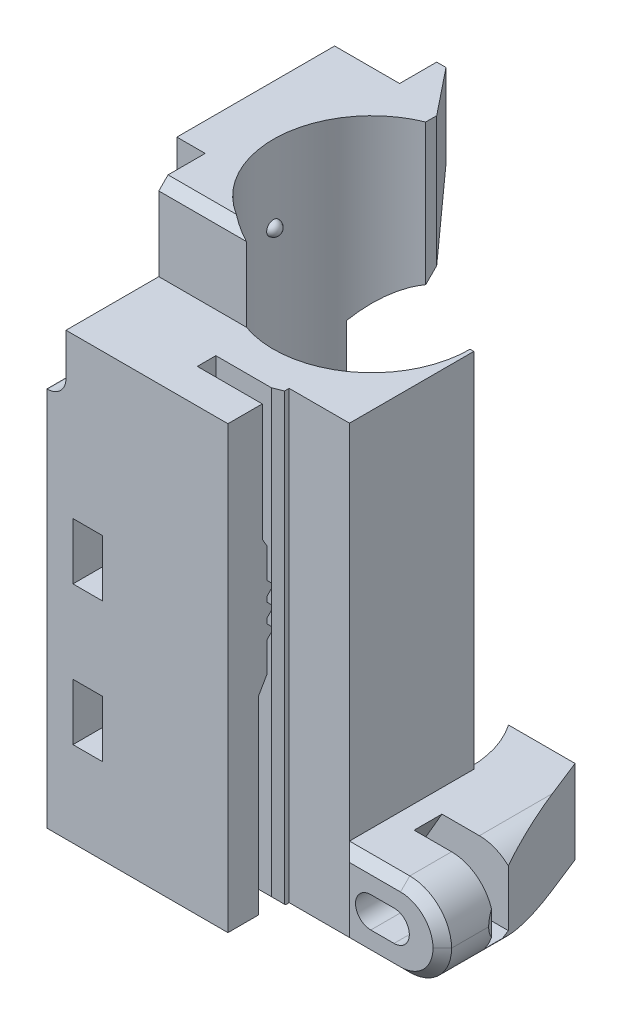
SolidWorks part; units mm, degrees
material "Custom Plastic"
ref_plane "Front Plane" through (0, 0, 0) normal (0, 0, 1) x (1, 0, 0)
ref_plane "Top Plane" through (0, 0, 0) normal (0, 1, 0) x (1, 0, 0)
ref_plane "Right Plane" through (0, 0, 0) normal (1, 0, 0) x (0, 0, -1)
sketch "Sketch2" plane through (0, 0, 0) normal (0, 1, 0) x (1, 0, 0)
  line L0 (22, -14.4) -> (22, -9.4)
  line L1 (16, 6) -> (16, -12.9) construction
  line L2 (11, -13.4) -> (4.5, -13.4)
  line L3 (4.5, -13.4) -> (4.5, -20)
  line L4 (4.5, -20) -> (-15, -20)
  line L5 (-15, -20) -> (-15, 16)
  line L6 (22, -9.4) -> (14.1647, -9.4) construction
  line L7 (8.7384, 6) -> (15.906, 6)
  line L8 (-15, 16) -> (-4, 16)
  line L9 (-4, 16) -> (-4, 9.8163)
  line L10 (11, -13.4) -> (12, -14.4)
  line L11 (12, -14.4) -> (22, -14.4)
  line L12 (22, -9.4) -> (15.906, 6)
  circle A0 centre (0, 0) radius 10.5 construction
  arc A1 (-4, 9.8163) -> (8.7384, 6) centre (0, 0) ccw
  arc A3 (14.1647, -9.4) -> (15.906, 6) centre (0, 0) ccw construction
  dimension "D1" = 21
  dimension "D2" = 0.1
  dimension "D11" = 17
  dimension "D3" = 4.5
  dimension "D4" = 16
  dimension "D5" = 15
  dimension "D6" = 13.4
  dimension "D7" = 20
  dimension "D8" = 16
  dimension "D9" = 4
  dimension "D10" = 6
  dimension "D12" = 22
  dimension "D14" = 45
  dimension "D15" = 11
  dimension "D16" = 1
extrude "Boss-Extrude1" add sketch "Sketch2" along normal blind 37 and the other way blind 20
sketch "Sketch3" plane through (0, 0, 0) normal (0, -1, 0) x (1, 0, 0)
  circle A0 centre (0, 0) radius 10.5
  dimension "D1" = 21
extrude "Cut-Extrude1" [suppressed] cut sketch "Sketch3" against normal blind 20 from offset 4 offset against normal yes
mirror "Mirror1" [suppressed] about plane through (0, 0, 0) normal (0, 1, 0)
sketch "Sketch4" plane through (0, 37, 0) normal (0, -1, 0) x (1, 0, 0)
  line L0 (4.5, 20) -> (4.5, 13.4) construction
  line L1 (-15, 20) -> (4.5, 20)
  line L2 (-15, 20) -> (-15, 9.9962)
  line L3 (-15, 9.9962) -> (4.5, 9.9962)
  line L4 (4.5, 20) -> (4.5, 9.9962)
extrude "Cut-Extrude3" [suppressed] cut sketch "Sketch4" along normal blind 11
sketch "Sketch5" plane through (4.5, 0, 0) normal (1, 0, 0) x (0, 0, -1)
  line L0 (-15.8, 5.718) -> (-15.3, 6.218)
  line L1 (-14.3, -20) -> (-16.3, -20)
  line L2 (-14.3, -20) -> (-14.3, 37)
  line L3 (-16.3, 37) -> (-14.3, 37)
  line L4 (-15.8, 2.5) -> (-15.8, 5.718)
  line L5 (-15.3, 6.218) -> (-15.3, 6.718)
  line L6 (-15.3, 6.718) -> (-15.8, 7.218)
  line L7 (-15.8, 9.782) -> (-15.3, 10.282)
  line L8 (-15.3, 10.282) -> (-15.3, 10.782)
  line L9 (-15.3, 10.782) -> (-15.8, 11.282)
  line L10 (-15.8, 7.75) -> (-15.3, 8.25)
  line L11 (-15.3, 8.25) -> (-15.3, 8.75)
  line L12 (-15.3, 8.75) -> (-15.8, 9.25)
  line L13 (-15.8, 9.25) -> (-15.8, 9.782)
  line L14 (-15.8, 2.5) -> (-16.3, 1.634)
  line L15 (-15.8, 7.218) -> (-15.8, 7.75)
  line L16 (-16.3, 1.634) -> (-16.3, -20)
  line L17 (-15.8, 11.282) -> (-15.8, 14.5)
  line L18 (-15.8, 14.5) -> (-16.3, 15.366)
  line L19 (-20, -20) -> (-13.4, -20) construction
  line L20 (16, 8.5) -> (-15.3, 8.5) construction
  line L21 (-16.3, 15.366) -> (-16.3, 37)
  line L22 (-20, 37) -> (-13.4, 37) construction
  line L23 (16, -20) -> (16, 37) construction
  dimension "D1" = 0.5
  dimension "D2" = 0.5
  dimension "D3" = 2.032
  dimension "D4" = 1.5
  dimension "D5" = 2
  dimension "D6" = 14.3
  dimension "D7" = 6
  dimension "D8" = 150
extrude "Cut-Extrude5" cut sketch "Sketch5" against normal blind 7
chamfer "Chamfer1" [suppressed] distance 1.2 angle 45
chamfer "Chamfer3" distance 0.5 angle 45 9 edges at (1, -20, 14.3) (-3.0421, -20, 10.1541) (-4, -20, -12.9082) (-9.5, -20, -16) (-15, -20, 2) (-5.25, -20, 20) (4.5, -20, 18.15) (1, -20, 16.3) (-2.5, -20, 15.3)
sketch "Sketch6" plane through (-15, 0, 0) normal (-1, 0, 0) x (0, 0, 1)
  line L0 (13, 7.5) -> (13, -7.5) construction
  line L1 (0, 0) -> (13, 0) construction
  circle A0 centre (13, 7.5) radius 1.55
  circle A1 centre (13, -7.5) radius 1.55
  dimension "D2" = 3.1
  dimension "D1" = 15
  dimension "D3" = 13
extrude "Cut-Extrude6" cut sketch "Sketch6" against normal blind 10
sketch "Sketch7" plane through (-15, 0, 0) normal (-1, 0, 0) x (0, 0, 1)
  line L0 (21.3141, -4.2) -> (21.3141, -10.3)
  line L1 (9.3668, -7.5) -> (10.9834, -10.3)
  line L2 (10.9834, -10.3) -> (21.3141, -10.3)
  line L3 (11.3834, 4.7) -> (9.7668, 7.5)
  line L4 (21.3141, 4.7) -> (11.3834, 4.7)
  line L5 (21.3141, -4.7) -> (11.3834, -4.7) construction
  line L6 (11.2721, -4.2) -> (9.3668, -7.5)
  line L7 (-3, 8.5) -> (19.4531, 8.5) construction
  line L8 (11.2721, -4.2) -> (21.3141, -4.2)
  line L9 (11.3834, 10.3) -> (21.7141, 10.3) construction
  line L10 (13.1374, -12.1691) -> (15.0359, -8.8809) construction
  line L11 (16.6078, -8.8418) -> (15.5516, -7.0123) construction
  line L12 (9.7668, 7.5) -> (11.6721, 10.8)
  line L13 (21.3141, 4.7) -> (21.3141, 10.8)
  line L14 (11.6721, 10.8) -> (21.3141, 10.8)
  circle A0 centre (12.6, -7.5) radius 2.8 construction
  circle A2 centre (13, 7.5) radius 2.8 construction
  circle A3 centre (13, 7.5) radius 1.55 construction
  point P4 (13, -7.5)
  dimension "D1" = 5.6
  dimension "D2" = 0.4
  dimension "D3" = 0.5
  dimension "D4" = 0.5
extrude "Cut-Extrude7" cut sketch "Sketch7" against normal blind 3.2 from offset 2.8 offset against normal yes
sketch "Sketch9" plane through (-15, 0, 0) normal (-1, 0, 0) x (0, 0, 1)
  line L0 (-16, 28) -> (-6, 18)
  line L1 (-16, -19.5) -> (-16, 37) construction
  line L2 (-6, 18) -> (-6, -20)
  line L3 (-16, -20) -> (20, -20) construction
  line L4 (-6, -20) -> (-16, -20)
  line L5 (-16, -20) -> (-16, 28)
  line L6 (-16, 37) -> (20, 37) construction
  dimension "D1" = 9
  dimension "D2" = 6
  dimension "D3" = 45
extrude "Cut-Extrude9" cut sketch "Sketch9" against normal blind 12 and the other way blind 10
sketch "Sketch12" plane through (-15, 0, 0) normal (-1, 0, 0) x (0, 0, 1)
  line L0 (8, 37) -> (8, 30)
  line L1 (-16, 37) -> (20, 37) construction
  line L2 (5, 25) -> (-13, 25)
  line L3 (-16, 28) -> (-13, 25)
  line L4 (-16, 28) -> (-6, 18) construction
  line L5 (-16, 28) -> (-16, 37)
  line L6 (-16, 37) -> (8, 37)
  line L7 (8, 30) -> (5, 30)
  line L8 (5, 30) -> (5, 25)
  dimension "D1" = 24
  dimension "D2" = 12
  dimension "D3" = 3
  dimension "D4" = 5
extrude "Boss-Extrude2" add sketch "Sketch12" along normal blind 1
sketch "Sketch10" plane through (0, 0, -16) normal (0, 0, -1) x (-1, 0, 0)
  line L1 (16, 37) -> (9, 37)
  line L2 (16, 37) -> (16, 28.8)
  line L3 (16, 28.8) -> (9, 28.8)
  line L4 (9, 37) -> (9, 28.8)
  line L5 (16, 37) -> (16, 28) construction
  line L6 (4, 28) -> (16, 28) construction
  line L7 (4, 37) -> (16, 37) construction
  dimension "D1" = 7
  dimension "D3" = 0.8
extrude "Cut-Extrude10" cut sketch "Sketch10" against normal blind 4
sketch "Sketch11" plane through (-16, 0, 0) normal (-1, 0, 0) x (0, 0, 1)
  line L0 (-12, 28.8) -> (-16, 28.8) construction
  line L2 (-16, 28) -> (-16, 28.8) construction
  circle A0 centre (-9, 26.3) radius 1.25
  circle A1 centre (1, 26.3) radius 1.25
  dimension "D3" = 10
  dimension "D4" = 2.5
  dimension "D1" = 2.5
  dimension "D2" = 7
extrude "Cut-Extrude11" cut sketch "Sketch11" against normal blind 4
chamfer "Chamfer4" distance 3 angle 45 2 edges
sketch "Sketch13" plane through (0, 37, 0) normal (0, 1, 0) x (1, 0, 0)
  line L0 (-16, -10) -> (0, -10)
  line L1 (0, -10) -> (0, 6.4112)
  line L2 (-16, -10) -> (-16, -20)
  line L3 (12, -20) -> (-16, -20)
  line L4 (0, 6.4112) -> (12, 6.4112)
  line L5 (12, -20) -> (12, 6.4112)
  line L7 (-15, -20) -> (4.5, -20) construction
extrude "Cut-Extrude12" cut sketch "Sketch13" against normal blind 9
chamfer "Chamfer5" distance 1 angle 45 1 edges at (-9.7578, 37, 10)
sketch "Sketch15" plane through (0, -20, -7.1) normal (0, 1, 0) x (1, 0, 0)
  line L1 (22, -21.5) -> (11, -21.5)
  line L2 (22, -21.5) -> (22, -1.1)
  line L3 (22, -1.1) -> (8.1933, -1.1)
  line L4 (11, -21.5) -> (11, -7.1)
  line L5 (11, -7.1) -> (8.1933, -7.1)
  line L6 (8.1933, -7.1) -> (8.1933, -1.1)
  dimension "D1" = 11
extrude "Cut-Extrude14" cut sketch "Sketch15" along normal through all from offset 9
chamfer "Chamfer6" distance 1 angle 45 1 edges at (-15, -0.75, -6)
chamfer "Chamfer7" distance 0.4 distance2 1 1 edges at (4.5, 4.25, 14.3) first distance on face at (4.5, -0.7, 13.84)
chamfer "Chamfer10" distance 0.4 distance2 2 1 edges at (4.5, -8.933, 16.3) first distance on face at (4.5, 7.65, 16.17)
sketch "Sketch17" plane through (0, 0, 14.4) normal (0, 0, 1) x (1, 0, 0)
  line L0 (15.55, -15.5) -> (22, -15.5) construction
  line L1 (22, -20) -> (22, -11) construction
  line L2 (14.3, -15.5) -> (16.8, -15.5) construction
  line L3 (14.3, -13.85) -> (16.8, -13.85)
  line L4 (14.3, -17.15) -> (16.8, -17.15)
  circle A0 centre (15.55, -15.5) radius 4.5 construction
  arc A1 (14.3, -13.85) -> (14.3, -17.15) centre (14.3, -15.5) ccw
  arc A2 (16.8, -17.15) -> (16.8, -13.85) centre (16.8, -15.5) ccw
  point P2 (11.05, -15.5)
  point P9 (15.55, -15.5)
  dimension "D2" = 9
  dimension "D3" = 1.65
  dimension "D1" = 11.05
  dimension "D4" = 2.5
extrude "Cut-Extrude16" cut sketch "Sketch17" against normal blind 6
fillet "Fillet2" radius 4.5 2 edges at (22, -11, 11.9) (22, -20, 11.9)
sketch "Sketch18" plane through (0, 0, 14.4) normal (0, 0, -1) x (-1, 0, 0)
  line L0 (-22.7084, -8.1113) -> (-22.7084, -18.3)
  line L1 (-10.8668, -15.5) -> (-15.1327, -8.1113)
  line L3 (-22.7084, -8.1113) -> (-15.1327, -8.1113)
  line L5 (-22.7084, -18.3) -> (-12.4834, -18.3)
  line L6 (-12.4834, -18.3) -> (-10.8668, -15.5)
  line L9 (-16.4286, -13.9332) -> (-17.2368, -15.3332) construction
  line L10 (-17.3332, -15.5) -> (-15.3536, -18.9286) construction
  line L11 (-12.4834, -12.7) -> (-14.1, -12.7) [skipped]
  circle A0 centre (-14.1, -15.5) radius 2.8 construction
  arc A3 (-14.3, -17.15) -> (-14.3, -13.85) centre (-14.3, -15.5) ccw construction
  point P10 (-14.3, -15.5)
  dimension "D2" = 5.6
  dimension "D1" = 0.2
extrude "Cut-Extrude17" cut sketch "Sketch18" against normal blind 0.5 and the other way blind 2.5 from offset 6
chamfer "Chamfer14" distance 1 angle 45 4 edges at (14.75, -11, 14.4) (20.682, -12.318, 14.4) (20.682, -18.682, 14.4) (14.75, -20, 14.4)
sketch "Sketch19" plane through (0, 0, 20) normal (0, 0, 1) x (1, 0, 0)
  line L0 (-16, 37) -> (-12.95, 37)
  line L1 (-12.95, 37) -> (-12.95, 23.5001)
  line L2 (-14.95, 21.5001) -> (-16, 21.5001)
  line L4 (-16, 37) -> (-5.6, 37) construction
  line L6 (-15, 28) -> (4.5, 28) construction
  line L8 (-16, 37) -> (-16, 21.5001)
  line L10 (-15, -19.5) -> (-15, 28) construction
  line L12 (-16, 33.5678) -> (-13.6361, 31.5078) construction
  line L13 (-16, 30) -> (-16, 36) construction
  arc A0 (-12.95, 30) -> (-13.6361, 31.5078) centre (-14.95, 30) ccw construction
  arc A1 (-14.95, 21.5001) -> (-12.95, 23.5001) centre (-14.95, 23.5001) ccw
  dimension "D1" = 4
  dimension "D2" = 2.05
  dimension "D3" = 2
extrude "Cut-Extrude18" cut sketch "Sketch19" against normal blind 15
chamfer "Chamfer15" distance 4 distance2 5 1 edges at (-4, 32.5, -16) first distance on face at (-9.6667, 31.2667, -16)
sketch "Sketch20" plane through (0, 0, 0) normal (0, 0, 1) x (1, 0, 0)
  line L1 (-10.6, 28.75) -> (-10.6, -14.25) construction
  line L2 (-10.6, 4.25) -> (4.5, 4.25) construction
  line L3 (4.5, -19.5) -> (4.5, 28) construction
  line L4 (-10.6, 28) -> (-10.6, 29.5)
  line L5 (-10.6, -13.5) -> (-10.6, -15)
  line L6 (4, -20) -> (-14.5, -20) construction
  arc A0 (-10.6, 29.5) -> (-10.6, 28) centre (-10.6, 28.75) ccw
  arc A1 (-10.6, -13.5) -> (-10.6, -15) centre (-10.6, -14.25) ccw
  dimension "D2" = 1.5
  dimension "D3" = 5.75
  dimension "D1" = 43
revolve "Revolve2" add sketch "Sketch20" angle 360 about L1
ref_axis "Axis1" through (0, -19.5, 0) along (0, 1, 0)
equation "\"y-plate-thickness\"=5"
equation "\"bed-plate-thickness\"=3"
equation "\"x-plate-thickness\"=5"
equation "\"rod-diameter\"=12"
equation "\"D1@Sketch15\"=\"rod-diameter\"/2+\"x-plate-thickness\""
